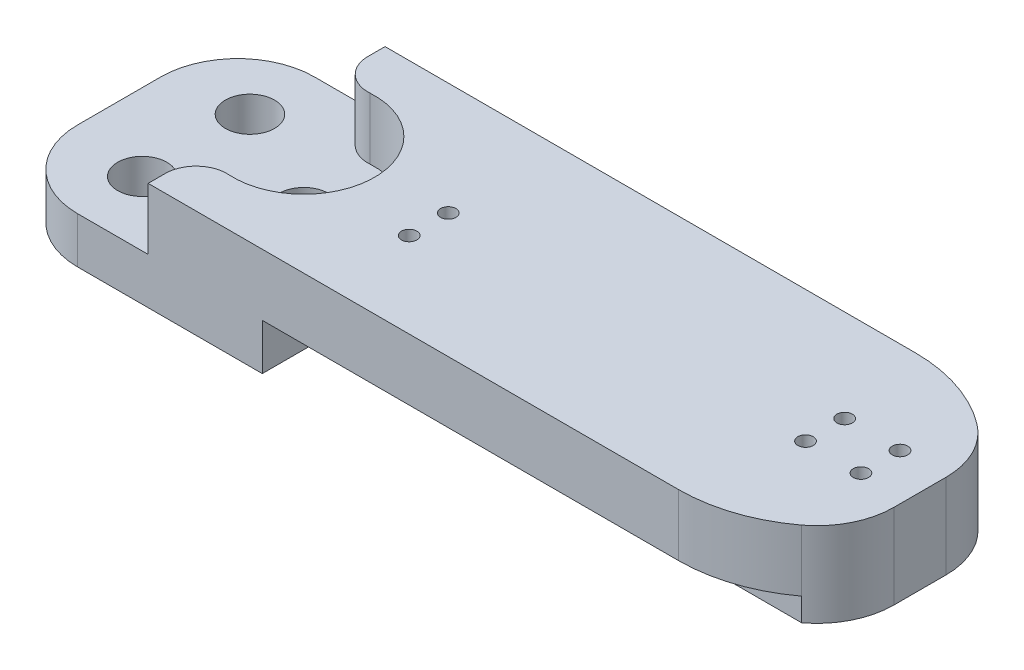
SolidWorks part; units mm, degrees
ref_plane "前视基准面" through (0, 0, 0) normal (0, 0, 1) x (1, 0, 0)
ref_plane "上视基准面" through (0, 0, 0) normal (0, 1, 0) x (1, 0, 0)
ref_plane "右视基准面" through (0, 0, 0) normal (1, 0, 0) x (0, 0, -1)
other "Configuration Table"
sketch "草图1" plane through (0, 0, 0) normal (0, 1, 0) x (1, 0, 0)
  line L0 (93.0116, 72.586) -> (93.0217, 72.586)
  line L1 (93.0116, 72.586) -> (93.0116, 72.6063)
  line L2 (93.0116, 72.586) -> (93.0217, 72.586)
  line L3 (93.0116, 72.586) -> (93.0116, 72.6063)
  line L4 (93.0116, 72.586) -> (93.0217, 72.586)
  line L5 (93.0116, 72.586) -> (93.0116, 72.6063)
  line L6 (103.9336, 94.432) -> (103.9437, 94.432)
  line L7 (103.9336, 94.432) -> (103.9336, 94.4523)
  line L8 (168.0366, 84.272) -> (168.0366, 84.2822)
  line L9 (168.0366, 84.272) -> (168.0163, 84.272)
  line L10 (158.1141, 95.514) -> (158.1039, 95.514)
  line L11 (158.1141, 95.514) -> (158.1141, 95.4938)
  line L12 (107.4956, 78.486) -> (107.4956, 78.4759)
  line L13 (107.4956, 78.486) -> (107.5158, 78.486)
  line L14 (161.3376, 94.432) -> (161.3477, 94.432)
  line L15 (161.3376, 94.432) -> (161.3376, 94.4523)
  line L16 (98.6366, 91.661) -> (98.6366, 91.6712)
  line L17 (98.6366, 91.661) -> (98.6163, 91.661)
  line L18 (100.7956, 90.686) -> (100.7956, 90.6962)
  line L19 (100.7956, 90.686) -> (100.7753, 90.686)
  line L20 (164.6396, 89.352) -> (164.6294, 89.352)
  line L21 (164.6396, 89.352) -> (164.6396, 89.3318)
  line L22 (94.7616, 80.161) -> (94.7514, 80.161)
  line L23 (94.7616, 80.161) -> (94.7616, 80.1408)
  line L24 (168.1956, 81.732) -> (168.1854, 81.732)
  line L25 (168.1956, 81.732) -> (168.1956, 81.7118)
  line L26 (178.2616, 97.586) -> (178.2514, 97.586)
  line L27 (178.2616, 97.586) -> (178.2616, 97.5658)
  line L28 (172.9366, 94.061) -> (172.9366, 94.0712)
  line L29 (172.9366, 94.061) -> (172.9163, 94.061)
  line L30 (113.8866, 87.236) -> (113.8764, 87.236)
  line L31 (113.8866, 87.236) -> (113.8866, 87.2158)
  line L32 (165.6556, 84.272) -> (165.6556, 84.2619)
  line L33 (165.6556, 84.272) -> (165.6758, 84.272)
  line L34 (115.6116, 92.886) -> (115.6116, 92.8759)
  line L35 (115.6116, 92.886) -> (115.6318, 92.886)
  line L36 (99.6366, 91.636) -> (99.6366, 91.6462)
  line L37 (99.6366, 91.636) -> (99.6163, 91.636)
  line L38 (106.2116, 94.486) -> (106.2217, 94.486)
  line L39 (106.2116, 94.486) -> (106.2116, 94.5063)
  line L40 (176.0696, 87.066) -> (176.0696, 87.0762)
  line L41 (176.0696, 87.066) -> (176.0493, 87.066)
  line L42 (175.5866, 82.236) -> (175.5967, 82.236)
  line L43 (175.5866, 82.236) -> (175.5866, 82.2563)
  line L44 (175.5616, 90.368) -> (175.5717, 90.368)
  line L45 (175.5616, 90.368) -> (175.5616, 90.3883)
  line L46 (95.0616, 85.036) -> (95.0514, 85.036)
  line L47 (95.0616, 85.036) -> (95.0616, 85.0158)
  line L48 (170.3616, 84.526) -> (170.3616, 84.5159)
  line L49 (170.3616, 84.526) -> (170.3818, 84.526)
  line L50 (156.2576, 97.48) -> (156.2576, 97.4699)
  line L51 (156.2576, 97.48) -> (156.2778, 97.48)
  line L52 (165.4016, 77.414) -> (165.4016, 77.4039)
  line L53 (165.4016, 77.414) -> (165.4218, 77.414)
  line L54 (166.1636, 90.368) -> (166.1737, 90.368)
  line L55 (166.1636, 90.368) -> (166.1636, 90.3883)
  line L56 (170.4816, 89.098) -> (170.4816, 89.1082)
  line L57 (170.4816, 89.098) -> (170.4613, 89.098)
  line L58 (114.7116, 89.836) -> (114.7116, 89.8462)
  line L59 (114.7116, 89.836) -> (114.6913, 89.836)
  line L60 (174.4366, 96.386) -> (174.4366, 96.3962)
  line L61 (174.4366, 96.386) -> (174.4163, 96.386)
  line L62 (186.9916, 88.59) -> (186.9916, 88.5799)
  line L63 (186.9916, 88.59) -> (187.0118, 88.59)
  line L64 (103.7141, 76.086) -> (103.7242, 76.086)
  line L65 (103.7141, 76.086) -> (103.7141, 76.1063)
  line L66 (184.9436, 88.0845) -> (184.9436, 88.0744)
  line L67 (184.9436, 88.0845) -> (184.9638, 88.0845)
  line L68 (122.8116, 84.011) -> (122.8217, 84.011)
  line L69 (122.8116, 84.011) -> (122.8116, 84.0313)
  line L70 (120.9516, 99.512) -> (120.9414, 99.512)
  line L71 (120.9516, 99.512) -> (120.9516, 99.4918)
  line L72 (173.1116, 80.97) -> (173.1116, 80.9802)
  line L73 (173.1116, 80.97) -> (173.0913, 80.97)
  line L74 (117.6116, 92.911) -> (117.6116, 92.9212)
  line L75 (117.6116, 92.911) -> (117.5913, 92.911)
  line L76 (112.3156, 92.908) -> (112.3257, 92.908)
  line L77 (112.3156, 92.908) -> (112.3156, 92.9283)
  line L78 (120.9516, 97.988) -> (120.9414, 97.988)
  line L79 (120.9516, 97.988) -> (120.9516, 97.9678)
  line L80 (163.1156, 87.32) -> (163.1156, 87.3099)
  line L81 (163.1156, 87.32) -> (163.1358, 87.32)
  line L82 (103.7141, 75.086) -> (103.7039, 75.086)
  line L83 (103.7141, 75.086) -> (103.7141, 75.0658)
  line L84 (116.6366, 92.886) -> (116.6366, 92.8962)
  line L85 (116.6366, 92.886) -> (116.6163, 92.886)
  line L86 (108.2516, 75.636) -> (108.2414, 75.636)
  line L87 (108.2516, 75.636) -> (108.2516, 75.6158)
  line L88 (185.9756, 88.082) -> (185.9756, 88.0922)
  line L89 (185.9756, 88.082) -> (185.9553, 88.082)
  line L90 (104.5616, 81.486) -> (104.5514, 81.486)
  line L91 (104.5616, 81.486) -> (104.5616, 81.4658)
  line L92 (101.8116, 90.686) -> (101.8116, 90.6962)
  line L93 (101.8116, 90.686) -> (101.7913, 90.686)
  line L94 (102.8616, 82.886) -> (102.8616, 82.8759)
  line L95 (102.8616, 82.886) -> (102.8818, 82.886)
  line L96 (106.2116, 95.486) -> (106.2217, 95.486)
  line L97 (106.2116, 95.486) -> (106.2116, 95.5063)
  line L98 (101.1396, 75.636) -> (101.1396, 75.6462)
  line L99 (101.1396, 75.636) -> (101.1193, 75.636)
  line L100 (97.0116, 90.486) -> (97.0014, 90.486)
  line L101 (97.0116, 90.486) -> (97.0116, 90.4658)
  line L102 (102.7866, 90.786) -> (102.7866, 90.7962)
  line L103 (102.7866, 90.786) -> (102.7663, 90.786)
  line L104 (167.7116, 87.911) -> (167.7116, 87.9009)
  line L105 (167.7116, 87.911) -> (167.7318, 87.911)
  line L106 (166.1636, 91.384) -> (166.1534, 91.384)
  line L107 (166.1636, 91.384) -> (166.1636, 91.3638)
  line L108 (97.0116, 89.486) -> (97.0014, 89.486)
  line L109 (97.0116, 89.486) -> (97.0116, 89.4658)
  line L110 (100.1236, 75.636) -> (100.1236, 75.6462)
  line L111 (100.1236, 75.636) -> (100.1033, 75.636)
  line L112 (172.0866, 80.62) -> (172.0866, 80.6302)
  line L113 (172.0866, 80.62) -> (172.0663, 80.62)
  line L114 (108.4991, 87.3235) -> (108.4991, 87.3337)
  line L115 (108.4991, 87.3235) -> (108.4788, 87.3235)
  line L116 (185.2136, 89.86) -> (185.2237, 89.86)
  line L117 (185.2136, 89.86) -> (185.2136, 89.8803)
  line L118 (173.2756, 88.844) -> (173.2756, 88.8339)
  line L119 (173.2756, 88.844) -> (173.2958, 88.844)
  line L120 (171.9366, 94.036) -> (171.9366, 94.0259)
  line L121 (171.9366, 94.036) -> (171.9568, 94.036)
  line L122 (170.2276, 93.924) -> (170.2276, 93.9139)
  line L123 (170.2276, 93.924) -> (170.2478, 93.924)
  line L124 (175.5866, 79.586) -> (175.5967, 79.586)
  line L125 (175.5866, 79.586) -> (175.5866, 79.6063)
  line L126 (180.5391, 83.002) -> (180.5492, 83.002)
  line L127 (180.5391, 83.002) -> (180.5391, 83.0223)
  line L128 (119.2116, 84.011) -> (119.2217, 84.011)
  line L129 (119.2116, 84.011) -> (119.2116, 84.0313)
  line L130 (107.7116, 74.186) -> (107.7217, 74.186)
  line L131 (107.7116, 74.186) -> (107.7116, 74.2063)
  line L132 (107.6116, 80.886) -> (107.6116, 80.8759)
  line L133 (107.6116, 80.886) -> (107.6318, 80.886)
  line L134 (103.7866, 91.561) -> (103.7866, 91.5712)
  line L135 (103.7866, 91.561) -> (103.7663, 91.561)
  line L136 (108.5866, 80.886) -> (108.5866, 80.8759)
  line L137 (108.5866, 80.886) -> (108.6068, 80.886)
  line L138 (165.5262, 99.6668) -> (182.5442, 99.6668)
  line L139 (182.5442, 99.6668) -> (182.5442, 96.8728)
  line L140 (96.8824, 77.3808) -> (96.6276, 77.6237)
  line L141 (96.6276, 77.6237) -> (96.3469, 77.836)
  line L142 (96.0438, 78.0149) -> (95.7224, 78.1582)
  line L143 (95.7224, 78.1582) -> (95.3867, 78.264)
  line L144 (164.7642, 100.4288) -> (165.5262, 99.6668)
  line L145 (164.5669, 88.1518) -> (164.4036, 88.0947)
  line L146 (164.4036, 88.0947) -> (164.2571, 88.0026)
  line L147 (164.2571, 88.0026) -> (164.1348, 87.8803)
  line L148 (164.1348, 87.8803) -> (164.0427, 87.7338)
  line L149 (164.1348, 86.917) -> (164.2571, 86.7947)
  line L150 (164.2571, 86.7947) -> (164.4036, 86.7026)
  line L151 (164.4036, 86.7026) -> (164.5669, 86.6455)
  line L152 (164.5669, 86.6455) -> (164.7388, 86.6261)
  line L153 (164.7388, 86.6261) -> (164.9107, 86.6455)
  line L154 (165.4919, 87.2267) -> (165.5113, 87.3986)
  line L155 (165.5113, 87.3986) -> (165.4919, 87.5705)
  line L156 (165.4919, 87.5705) -> (165.4348, 87.7338)
  line L157 (165.4348, 87.7338) -> (165.3427, 87.8803)
  line L158 (165.3427, 87.8803) -> (165.2204, 88.0026)
  line L159 (137.7132, 95.8568) -> (137.144, 95.8353)
  line L160 (151.1426, 85.7394) -> (151.3379, 85.9384)
  line L161 (151.8102, 87.2208) -> (151.7905, 87.499)
  line L162 (151.7905, 87.499) -> (151.7319, 87.7716)
  line L163 (151.7319, 87.7716) -> (151.6355, 88.0333)
  line L164 (151.6355, 88.0333) -> (151.5033, 88.2788)
  line L165 (151.5033, 88.2788) -> (151.3379, 88.5033)
  line L166 (139.9573, 95.5149) -> (139.4075, 95.6639)
  line L167 (139.4075, 95.6639) -> (138.8482, 95.7709)
  line L168 (138.8482, 95.7709) -> (138.2823, 95.8353)
  line L169 (138.2823, 95.8353) -> (137.7132, 95.8568)
  line L170 (118.0282, 100.4288) -> (164.7642, 100.4288)
  line L171 (182.5442, 96.8728) -> (182.6167, 96.5552)
  line L172 (118.0282, 98.6508) -> (118.0282, 100.4288)
  line L173 (182.6167, 96.5552) -> (182.7281, 96.249)
  line L174 (97.8352, 98.6508) -> (118.0282, 98.6508)
  line L175 (182.7281, 96.249) -> (182.8767, 95.9591)
  line L176 (97.8352, 94.5868) -> (97.8352, 98.6508)
  line L177 (182.8767, 95.9591) -> (183.0603, 95.6899)
  line L178 (97.8236, 94.2665) -> (97.8352, 94.5868)
  line L179 (183.0603, 95.6899) -> (183.2759, 95.4456)
  line L180 (97.7731, 93.95) -> (97.8236, 94.2665)
  line L181 (183.2759, 95.4456) -> (183.5202, 95.23)
  line L182 (97.6844, 93.642) -> (97.7731, 93.95)
  line L183 (183.5202, 95.23) -> (183.7894, 95.0464)
  line L184 (97.5587, 93.3471) -> (97.6844, 93.642)
  line L185 (183.7894, 95.0464) -> (184.0793, 94.8978)
  line L186 (97.398, 93.0697) -> (97.5587, 93.3471)
  line L187 (184.0793, 94.8978) -> (184.3855, 94.7864)
  line L188 (97.2046, 92.8141) -> (97.398, 93.0697)
  line L189 (184.3855, 94.7864) -> (184.7032, 94.7138)
  line L190 (96.9815, 92.5839) -> (97.2046, 92.8141)
  line L191 (184.7032, 94.7138) -> (188.8942, 94.7138)
  line L192 (96.732, 92.3827) -> (96.9815, 92.5839)
  line L193 (188.8942, 94.7138) -> (188.8942, 78.3308)
  line L194 (96.4599, 92.2134) -> (96.732, 92.3827)
  line L195 (188.8942, 78.3308) -> (177.4642, 78.3308)
  line L196 (96.169, 92.0786) -> (96.4599, 92.2134)
  line L197 (177.4642, 78.3308) -> (177.1354, 78.2515)
  line L198 (95.864, 91.9802) -> (96.169, 92.0786)
  line L199 (177.1354, 78.2515) -> (176.8186, 78.1328)
  line L200 (95.5492, 91.9198) -> (95.864, 91.9802)
  line L201 (176.8186, 78.1328) -> (176.5187, 77.9765)
  line L202 (93.0092, 91.9198) -> (95.5492, 91.9198)
  line L203 (176.5187, 77.9765) -> (176.2399, 77.7849)
  line L204 (93.0092, 88.1098) -> (93.0092, 91.9198)
  line L205 (176.2399, 77.7849) -> (175.9866, 77.5609)
  line L206 (95.5492, 88.1098) -> (93.0092, 88.1098)
  line L207 (175.9866, 77.5609) -> (175.7623, 77.3077)
  line L208 (95.7229, 88.0427) -> (95.5492, 88.1098)
  line L209 (175.7623, 77.3077) -> (175.5704, 77.0292)
  line L210 (95.878, 87.9395) -> (95.7229, 88.0427)
  line L211 (175.5704, 77.0292) -> (175.4138, 76.7294)
  line L212 (96.007, 87.8051) -> (95.878, 87.9395)
  line L213 (175.4138, 76.7294) -> (175.2949, 76.4128)
  line L214 (96.1038, 87.6459) -> (96.007, 87.8051)
  line L215 (175.2949, 76.4128) -> (175.2152, 76.084)
  line L216 (96.1638, 87.4695) -> (96.1038, 87.6459)
  line L217 (175.2152, 76.084) -> (175.1761, 75.7481)
  line L218 (96.1842, 87.2843) -> (96.1638, 87.4695)
  line L219 (175.1761, 75.7481) -> (175.1782, 75.4098)
  line L220 (96.1638, 87.0992) -> (96.1842, 87.2843)
  line L221 (175.1782, 75.4098) -> (175.1782, 75.0288)
  line L222 (96.1038, 86.9228) -> (96.1638, 87.0992)
  line L223 (175.1782, 75.0288) -> (161.4622, 75.0288)
  line L224 (96.007, 86.7636) -> (96.1038, 86.9228)
  line L225 (161.4622, 75.0288) -> (161.4622, 72.6158)
  line L226 (95.878, 86.6292) -> (96.007, 86.7636)
  line L227 (161.4622, 72.6158) -> (97.5812, 72.6158)
  line L228 (95.7229, 86.526) -> (95.878, 86.6292)
  line L229 (97.5812, 72.6158) -> (97.5812, 76.1718)
  line L230 (95.5492, 86.4588) -> (95.7229, 86.526)
  line L231 (97.5812, 76.1718) -> (97.4595, 76.5021)
  line L232 (93.0092, 86.4588) -> (95.5492, 86.4588)
  line L233 (97.4595, 76.5021) -> (97.301, 76.8164)
  line L234 (93.0092, 78.3308) -> (93.0092, 86.4588)
  line L235 (97.301, 76.8164) -> (97.1078, 77.1105)
  line L236 (95.0412, 78.3308) -> (93.0092, 78.3308)
  line L237 (97.1078, 77.1105) -> (96.8824, 77.3808)
  line L238 (95.3867, 78.264) -> (95.0412, 78.3308)
  line L239 (138.4395, 78.6481) -> (139.0038, 78.7263)
  line L240 (137.871, 78.6089) -> (138.4395, 78.6481)
  line L241 (137.3013, 78.6089) -> (137.871, 78.6089)
  line L242 (96.3469, 77.836) -> (96.0438, 78.0149)
  line L243 (164.7388, 88.1712) -> (164.5669, 88.1518)
  line L244 (164.9107, 88.1518) -> (164.7388, 88.1712)
  line L245 (165.0739, 88.0947) -> (164.9107, 88.1518)
  line L246 (165.2204, 88.0026) -> (165.0739, 88.0947)
  line L247 (134.0044, 79.4194) -> (134.5262, 79.1906)
  line L248 (133.4996, 79.6836) -> (134.0044, 79.4194)
  line L249 (133.0142, 79.9818) -> (133.4996, 79.6836)
  line L250 (123.9972, 85.6968) -> (133.0142, 79.9818)
  line L251 (123.8108, 85.8961) -> (123.9972, 85.6968)
  line L252 (165.4348, 87.0635) -> (165.4919, 87.2267)
  line L253 (165.3427, 86.917) -> (165.4348, 87.0635)
  line L254 (165.2204, 86.7947) -> (165.3427, 86.917)
  line L255 (165.0739, 86.7026) -> (165.2204, 86.7947)
  line L256 (164.9107, 86.6455) -> (165.0739, 86.7026)
  line L257 (123.3808, 87.4295) -> (123.3622, 87.1573)
  line L258 (123.4363, 87.6966) -> (123.3808, 87.4295)
  line L259 (123.5278, 87.9536) -> (123.4363, 87.6966)
  line L260 (123.6534, 88.1958) -> (123.5278, 87.9536)
  line L261 (123.8108, 88.4186) -> (123.6534, 88.1958)
  line L262 (164.0427, 87.0635) -> (164.1348, 86.917)
  line L263 (163.9856, 87.2267) -> (164.0427, 87.0635)
  line L264 (163.9662, 87.3986) -> (163.9856, 87.2267)
  line L265 (163.9856, 87.5705) -> (163.9662, 87.3986)
  line L266 (164.0427, 87.7338) -> (163.9856, 87.5705)
  line L267 (136.5782, 95.7709) -> (136.0188, 95.6639)
  line L268 (137.144, 95.8353) -> (136.5782, 95.7709)
  line L269 (186.4304, 92.0214) -> (186.4304, 93.139)
  line L270 (184.5508, 92.0214) -> (186.4304, 92.0214)
  line L271 (179.928, 93.139) -> (179.928, 92.0214)
  line L272 (181.8076, 93.139) -> (179.928, 93.139)
  line L273 (181.8076, 92.0214) -> (181.8076, 93.139)
  line L274 (140.4941, 95.3249) -> (139.9573, 95.5149)
  line L275 (141.0152, 95.0948) -> (140.4941, 95.3249)
  line L276 (150.9212, 88.8718) -> (141.0152, 95.0948)
  line L277 (151.1426, 88.7023) -> (150.9212, 88.8718)
  line L278 (151.3379, 88.5033) -> (151.1426, 88.7023)
  line L279 (176.7784, 94.9678) -> (176.7784, 93.0882)
  line L280 (177.896, 94.9678) -> (176.7784, 94.9678)
  line L281 (177.896, 93.0882) -> (177.896, 94.9678)
  line L282 (176.7784, 93.0882) -> (177.896, 93.0882)
  line L283 (171.038, 98.3206) -> (171.038, 97.203)
  line L284 (151.7905, 86.9427) -> (151.8102, 87.2208)
  line L285 (151.7319, 86.6701) -> (151.7905, 86.9427)
  line L286 (151.6355, 86.4084) -> (151.7319, 86.6701)
  line L287 (151.5033, 86.1629) -> (151.6355, 86.4084)
  line L288 (151.3379, 85.9384) -> (151.5033, 86.1629)
  line L289 (163.4688, 97.3554) -> (163.4688, 98.473)
  line L290 (150.9212, 85.5698) -> (151.1426, 85.7394)
  line L291 (142.1582, 79.9818) -> (150.9212, 85.5698)
  line L292 (141.6727, 79.6836) -> (142.1582, 79.9818)
  line L293 (141.1679, 79.4194) -> (141.6727, 79.6836)
  line L294 (140.6461, 79.1906) -> (141.1679, 79.4194)
  line L295 (140.1098, 78.9982) -> (140.6461, 79.1906)
  line L296 (139.5615, 78.8432) -> (140.1098, 78.9982)
  line L297 (139.0038, 78.7263) -> (139.5615, 78.8432)
  line L298 (136.7328, 78.6481) -> (137.3013, 78.6089)
  line L299 (136.1685, 78.7263) -> (136.7328, 78.6481)
  line L300 (135.6108, 78.8432) -> (136.1685, 78.7263)
  line L301 (135.0625, 78.9982) -> (135.6108, 78.8432)
  line L302 (134.5262, 79.1906) -> (135.0625, 78.9982)
  line L303 (134.4112, 95.0948) -> (123.9972, 88.6178)
  line L304 (134.9322, 95.3249) -> (134.4112, 95.0948)
  line L305 (179.928, 92.0214) -> (181.8076, 92.0214)
  line L306 (182.2648, 93.9518) -> (182.2648, 92.8342)
  line L307 (184.1444, 93.9518) -> (182.2648, 93.9518)
  line L308 (123.6534, 86.1189) -> (123.8108, 85.8961)
  line L309 (123.5278, 86.3611) -> (123.6534, 86.1189)
  line L310 (123.4363, 86.6181) -> (123.5278, 86.3611)
  line L311 (123.3808, 86.8852) -> (123.4363, 86.6181)
  line L312 (123.3622, 87.1573) -> (123.3808, 86.8852)
  line L313 (135.469, 95.5149) -> (134.9322, 95.3249)
  line L314 (136.0188, 95.6639) -> (135.469, 95.5149)
  line L315 (172.9176, 98.3206) -> (171.038, 98.3206)
  line L316 (172.9176, 97.203) -> (172.9176, 98.3206)
  line L317 (171.038, 97.203) -> (172.9176, 97.203)
  line L318 (123.9972, 88.6178) -> (123.8108, 88.4186)
  line L319 (161.5892, 98.473) -> (161.5892, 97.3554)
  line L320 (163.4688, 98.473) -> (161.5892, 98.473)
  line L321 (157.6268, 97.3554) -> (159.5064, 97.3554)
  line L322 (161.5892, 97.3554) -> (163.4688, 97.3554)
  line L323 (159.5064, 98.473) -> (157.6268, 98.473)
  line L324 (159.5064, 97.3554) -> (159.5064, 98.473)
  line L325 (184.1444, 92.8342) -> (184.1444, 93.9518)
  line L326 (186.4304, 93.139) -> (184.5508, 93.139)
  line L327 (184.5508, 93.139) -> (184.5508, 92.0214)
  line L328 (182.2648, 92.8342) -> (184.1444, 92.8342)
  line L329 (157.6268, 98.473) -> (157.6268, 97.3554)
  line L330 (119.5316, 81.791) -> (119.5316, 81.151)
  line L331 (118.8916, 81.151) -> (119.5316, 81.151)
  line L332 (118.8916, 81.791) -> (118.8916, 81.151)
  line L333 (118.8916, 81.791) -> (119.5316, 81.791)
  line L334 (119.5316, 84.331) -> (119.5316, 83.691)
  line L335 (118.8916, 84.331) -> (118.8916, 83.691)
  line L336 (118.8916, 84.331) -> (119.5316, 84.331)
  line L337 (118.8916, 83.691) -> (119.5316, 83.691)
  line L338 (122.4916, 81.791) -> (123.1316, 81.791)
  line L339 (122.4916, 81.151) -> (123.1316, 81.151)
  line L340 (122.4916, 81.791) -> (122.4916, 81.151)
  line L341 (123.1316, 81.791) -> (123.1316, 81.151)
  line L342 (123.1316, 84.331) -> (123.1316, 83.691)
  line L343 (122.4916, 83.691) -> (123.1316, 83.691)
  line L344 (122.4916, 84.331) -> (123.1316, 84.331)
  line L345 (122.4916, 84.331) -> (122.4916, 83.691)
  line L346 (94.4416, 79.841) -> (94.4416, 80.481)
  line L347 (95.0816, 80.481) -> (94.4416, 80.481)
  line L348 (95.0816, 79.841) -> (94.4416, 79.841)
  line L349 (95.0816, 79.841) -> (95.0816, 80.481)
  line L350 (94.4416, 82.381) -> (94.4416, 83.021)
  line L351 (95.0816, 83.021) -> (94.4416, 83.021)
  line L352 (95.0816, 82.381) -> (94.4416, 82.381)
  line L353 (95.0816, 82.381) -> (95.0816, 83.021)
  circle A0 centre (122.8116, 81.471) radius 0.5
  circle A1 centre (107.2241, 88.5985) radius 0.175
  circle A2 centre (109.7741, 86.0485) radius 0.175
  circle A3 centre (108.4991, 86.0485) radius 0.175
  circle A4 centre (107.2241, 86.0485) radius 0.175
  circle A5 centre (119.2116, 81.471) radius 0.5
  circle A6 centre (94.7616, 80.161) radius 0.5
  circle A7 centre (94.7616, 82.701) radius 0.5
  circle A8 centre (122.8116, 84.011) radius 0.5
  circle A9 centre (119.2116, 84.011) radius 0.5
  circle A10 centre (109.7741, 87.3235) radius 0.175
  circle A11 centre (108.4991, 87.3235) radius 0.175
  circle A12 centre (107.2241, 87.3235) radius 0.175
  circle A13 centre (109.7741, 88.5985) radius 0.175
  circle A14 centre (108.4991, 88.5985) radius 0.175
  point P204 (93.0116, 72.586)
  point P205 (93.0116, 72.586)
  point P206 (93.0116, 72.586)
  point P207 (103.9336, 94.432)
  point P208 (168.0366, 84.272)
  point P209 (158.1141, 95.514)
  point P210 (107.4956, 78.486)
  point P211 (161.3376, 94.432)
  point P212 (98.6366, 91.661)
  point P213 (100.7956, 90.686)
  point P214 (164.6396, 89.352)
  point P215 (94.7616, 80.161)
  point P216 (168.1956, 81.732)
  point P217 (178.2616, 97.586)
  point P218 (172.9366, 94.061)
  point P219 (113.8866, 87.236)
  point P220 (165.6556, 84.272)
  point P221 (115.6116, 92.886)
  point P222 (99.6366, 91.636)
  point P223 (106.2116, 94.486)
  point P224 (176.0696, 87.066)
  point P225 (175.5866, 82.236)
  point P226 (175.5616, 90.368)
  point P227 (95.0616, 85.036)
  point P228 (170.3616, 84.526)
  point P229 (156.2576, 97.48)
  point P230 (165.4016, 77.414)
  point P231 (166.1636, 90.368)
  point P232 (170.4816, 89.098)
  point P233 (114.7116, 89.836)
  point P234 (174.4366, 96.386)
  point P235 (186.9916, 88.59)
  point P236 (103.7141, 76.086)
  point P237 (184.9436, 88.0845)
  point P238 (122.8116, 84.011)
  point P239 (120.9516, 99.512)
  point P240 (173.1116, 80.97)
  point P241 (117.6116, 92.911)
  point P242 (112.3156, 92.908)
  point P243 (120.9516, 97.988)
  point P244 (163.1156, 87.32)
  point P245 (103.7141, 75.086)
  point P246 (116.6366, 92.886)
  point P247 (108.2516, 75.636)
  point P248 (185.9756, 88.082)
  point P249 (104.5616, 81.486)
  point P250 (101.8116, 90.686)
  point P251 (102.8616, 82.886)
  point P252 (106.2116, 95.486)
  point P253 (101.1396, 75.636)
  point P254 (97.0116, 90.486)
  point P255 (102.7866, 90.786)
  point P256 (167.7116, 87.911)
  point P257 (166.1636, 91.384)
  point P258 (97.0116, 89.486)
  point P259 (100.1236, 75.636)
  point P260 (172.0866, 80.62)
  point P261 (108.4991, 87.3235)
  point P262 (185.2136, 89.86)
  point P263 (173.2756, 88.844)
  point P264 (171.9366, 94.036)
  point P265 (170.2276, 93.924)
  point P266 (175.5866, 79.586)
  point P267 (180.5391, 83.002)
  point P268 (119.2116, 84.011)
  point P269 (107.7116, 74.186)
  point P270 (107.6116, 80.886)
  point P271 (103.7866, 91.561)
  point P272 (108.5866, 80.886)
sketch "草图2" plane through (0, 0, 0) normal (0, 1, 0) x (1, 0, 0)
  line L1 (125.8116, 76.6158) -> (90.7616, 76.6158)
  line L2 (125.8116, 76.6158) -> (125.8116, 88.011)
  line L3 (125.8116, 88.011) -> (90.7616, 88.011)
  line L4 (90.7616, 76.6158) -> (90.7616, 88.011)
  line L5 (125.8116, 76.6158) -> (90.7616, 88.011) construction
  line L6 (125.8116, 88.011) -> (90.7616, 76.6158) construction
  line L7 (161.4622, 72.6158) -> (97.5812, 72.6158) construction
  circle A0 centre (94.7616, 82.701) radius 0.6
  circle A1 centre (94.7616, 80.161) radius 0.6
  circle A2 centre (119.2116, 84.011) radius 0.6
  circle A3 centre (122.8116, 84.011) radius 0.6
  circle A4 centre (122.8116, 81.471) radius 0.6
  circle A5 centre (119.2116, 81.471) radius 0.6
  point P0 (94.7616, 82.701)
  point P1 (94.7616, 80.161)
  point P3 (119.2116, 84.011)
  point P5 (119.2116, 81.471)
  point P7 (122.8116, 84.011)
  point P9 (122.8116, 81.471)
  point P28 (108.2866, 82.3134)
  dimension "D1" = 1.2
  dimension "D2" = 3
  dimension "D3" = 4
  dimension "D4" = 4
  dimension "D5" = 4
extrude "凸台-拉伸1" add sketch "草图2" along normal blind 1.5
sketch "草图3" plane through (0, 1.5, 0) normal (0, 1, 0) x (1, 0, 0)
  line L12 (127.8116, 74.6158) -> (127.8116, 90.011)
  line L13 (127.8116, 90.011) -> (88.7616, 90.011)
  line L14 (88.7616, 90.011) -> (88.7616, 74.6158)
  line L15 (88.7616, 74.6158) -> (127.8116, 74.6158)
  line L16 (127.8116, 74.6158) -> (127.8116, 90.011)
  line L17 (127.8116, 90.011) -> (88.7616, 90.011)
  line L18 (88.7616, 90.011) -> (88.7616, 74.6158)
  line L19 (88.7616, 74.6158) -> (127.8116, 74.6158)
  circle A2 centre (94.7616, 82.701) radius 0.5
  circle A5 centre (94.7616, 80.161) radius 0.5
  circle A8 centre (119.2116, 84.011) radius 0.5
  circle A11 centre (122.8116, 84.011) radius 0.5
  circle A14 centre (122.8116, 81.471) radius 0.5
  circle A16 centre (119.2116, 81.471) radius 0.5
  dimension "D1" = 1
  dimension "D7" = 2
extrude "凸台-拉伸2" add sketch "草图3" along normal blind 4
sketch "草图4" plane through (0, 0, -90.011) normal (0, 0, -1) x (-1, 0, 0)
  line L0 (-127.8116, 1.5) -> (-88.7616, 1.5) construction
  line L1 (-88.7616, 5.5) -> (-73.7616, 5.5)
  line L2 (-88.7616, 5.5) -> (-88.7616, 1.5)
  line L3 (-88.7616, 1.5) -> (-73.7616, 1.5)
  line L4 (-73.7616, 5.5) -> (-73.7616, 1.5)
  line L5 (-88.7616, 5.5) -> (-73.7616, 1.5) construction
  line L6 (-88.7616, 1.5) -> (-73.7616, 5.5) construction
  point P4 (-81.2616, 3.5)
  dimension "D1" = 15
extrude "凸台-拉伸3" add sketch "草图4" against normal up to surface (15.3952 mm away) up to face at (108.2866, 3.5, -74.6158)
sketch "草图5" plane through (0, 1.5, 0) normal (0, -1, 0) x (1, 0, 0)
  line L0 (127.8116, -90.011) -> (73.7616, -90.011) construction
  line L1 (73.7616, -74.6158) -> (90.7616, -74.6158)
  line L2 (73.7616, -74.6158) -> (73.7616, -90.011)
  line L3 (73.7616, -90.011) -> (90.7616, -90.011)
  line L4 (90.7616, -74.6158) -> (90.7616, -90.011)
  line L5 (73.7616, -74.6158) -> (90.7616, -90.011) construction
  line L6 (73.7616, -90.011) -> (90.7616, -74.6158) construction
  line L7 (90.7616, -88.011) -> (90.7616, -76.6158) construction
  point P4 (82.2616, -82.3134)
extrude "凸台-拉伸4" add sketch "草图5" along normal blind 3
sketch "草图6" plane through (0, -1.5, 0) normal (0, -1, 0) x (1, 0, 0)
  line L0 (73.7616, -82.3134) -> (90.7616, -82.3134) construction
  line L1 (73.7616, -74.6158) -> (73.7616, -90.011) construction
  line L2 (90.7616, -88.011) -> (90.7616, -76.6158) construction
  line L3 (78.7616, -74.6158) -> (78.7616, -90.011) construction
  line L4 (90.7616, -74.6158) -> (73.7616, -74.6158) construction
  line L5 (73.7616, -90.011) -> (90.7616, -90.011) construction
  circle A0 centre (78.7616, -78.8134) radius 1.6
  circle A1 centre (85.7616, -82.3134) radius 1.6
  circle A2 centre (78.7616, -85.8134) radius 1.6
  dimension "D1" = 3.2
  dimension "D2" = 7
  dimension "D3" = 7
  dimension "D4" = 5
extrude "切除-拉伸1" cut sketch "草图6" against normal through all
sketch "草图7" plane through (0, 5.5, 0) normal (0, 1, 0) x (1, 0, 0)
  circle A0 centre (78.7616, 85.8134) radius 1.6 construction
  arc A1 (83.343, 86.2263) -> (75.7766, 82.3134) centre (78.7616, 85.8134) ccw
  circle A8 centre (85.7616, 82.3134) radius 4.6
  arc A9 (83.343, 78.4006) -> (83.343, 86.2263) centre (85.7616, 82.3134) ccw
  circle A11 centre (78.7616, 78.8134) radius 4.6
  arc A12 (75.7766, 82.3134) -> (83.343, 78.4006) centre (78.7616, 78.8134) ccw
  dimension "D1" = 3
  dimension "D2" = 3
  dimension "D3" = 3
extrude "切除-拉伸2" cut sketch "草图7" against normal offset from surface (4 mm away) 3 up to face at (78.7616, -1.5, -80.4134)
sketch "草图8" plane through (0, 5.5, 0) normal (0, 1, 0) x (1, 0, 0)
  line L0 (89.6957, 79.9296) -> (83.343, 78.4006)
  line L1 (83.343, 78.4006) -> (80.6431, 74.6158)
  line L2 (80.6431, 74.6158) -> (92.689, 74.6158)
  line L9 (127.8116, 90.011) -> (80.6431, 90.011) construction
  line L10 (80.6431, 74.6158) -> (127.8116, 74.6158) construction
  line L11 (92.689, 90.011) -> (80.6431, 90.011)
  line L15 (80.6431, 90.011) -> (83.343, 86.2263)
  line L16 (83.343, 86.2263) -> (89.6957, 84.6973)
  line L18 (76.88, 90.011) -> (73.7616, 90.011)
  line L19 (73.7616, 90.011) -> (73.7616, 74.6158)
  line L20 (73.7616, 74.6158) -> (76.88, 74.6158)
  line L21 (76.88, 90.011) -> (73.7616, 90.011)
  line L22 (73.7616, 90.011) -> (73.7616, 74.6158)
  line L23 (73.7616, 74.6158) -> (76.88, 74.6158)
  arc A8 (92.689, 90.011) -> (89.6957, 84.6973) centre (92.689, 86.511) ccw
  arc A9 (89.6957, 79.9296) -> (92.689, 74.6158) centre (92.689, 78.1158) ccw
  arc A10 (83.343, 78.4006) -> (83.343, 86.2263) centre (85.7616, 82.3134) ccw construction
  arc A11 (83.343, 78.4006) -> (83.343, 86.2263) centre (85.7616, 82.3134) ccw construction
  arc A16 (76.88, 90.011) -> (75.7766, 82.3134) centre (78.7616, 85.8134) ccw
  arc A17 (75.7766, 82.3134) -> (76.88, 74.6158) centre (78.7616, 78.8134) ccw
  arc A18 (76.88, 90.011) -> (75.7766, 82.3134) centre (78.7616, 85.8134) ccw
  arc A19 (75.7766, 82.3134) -> (76.88, 74.6158) centre (78.7616, 78.8134) ccw
  dimension "D1" = 7
  dimension "D2" = 0
extrude "切除-拉伸4" cut sketch "草图8" against normal up to surface (4 mm away) contours A18 A19 L23 L22 L21 up to face at (85.7616, 1.5, -83.9134)
fillet "圆角2" radius 5 2 edges at (73.7616, 0, -90.011) (73.7616, 0, -74.6158)
sketch "草图9" plane through (0, 5.5, 0) normal (0, 1, 0) x (1, 0, 0)
  line L0 (83.343, 86.2263) -> (83.343, 90.011)
  line L1 (127.8116, 90.011) -> (80.6431, 90.011) construction
  line L2 (83.343, 90.011) -> (80.6431, 90.011)
  line L3 (80.6431, 90.011) -> (83.343, 86.2263)
  line L4 (83.343, 78.4006) -> (83.343, 74.6158)
  line L5 (80.6431, 74.6158) -> (127.8116, 74.6158) construction
  line L6 (83.343, 74.6158) -> (80.6431, 74.6158)
  line L7 (80.6431, 74.6158) -> (83.343, 78.4006)
extrude "切除-拉伸5" cut sketch "草图9" against normal up to surface (4 mm away) up to face at (79.8741, 1.5, -82.3134)
fillet "圆角3" radius 2 2 edges at (83.343, 3.5, -78.4006) (83.343, 3.5, -86.2263)
sketch "草图10" plane through (0, -1.5, 0) normal (0, -1, 0) x (1, 0, 0)
  line L0 (85.7616, -82.3134) -> (85.7616, -73.1344) construction
  line L1 (81.7616, -82.3134) -> (88.5604, -82.3134) construction
  circle A0 centre (81.7616, -82.3134) radius 0.6
  circle A1 centre (85.7616, -77.3134) radius 0.6
  circle A2 centre (85.7616, -87.3134) radius 0.6
  dimension "D3" = 1.2
  dimension "D1" = 10
  dimension "D2" = 4
extrude "切除-拉伸6" cut sketch "草图10" against normal blind 2
sketch "草图11" plane through (0, 0, 0) normal (0, -1, 0) x (1, 0, 0)
  line L0 (127.8116, -74.6158) -> (127.8116, -90.011) construction
  line L1 (90.7616, -74.6158) -> (127.8116, -74.6158) construction
  line L2 (127.8116, -90.011) -> (90.7616, -90.011) construction
  line L3 (117.8116, -74.6158) -> (127.8116, -74.6158)
  line L4 (127.8116, -74.6158) -> (127.8116, -84.6158)
  line L5 (127.8116, -90.011) -> (117.8116, -90.011)
  line L6 (127.8116, -80.011) -> (127.8116, -90.011)
  arc A0 (126.6883, -80.011) -> (117.8116, -74.6158) centre (117.8116, -84.6158) ccw
  arc A1 (117.8116, -90.011) -> (126.6883, -84.6158) centre (117.8116, -80.011) ccw
  arc A2 (126.6883, -84.6158) -> (126.6883, -80.011) centre (122.2499, -82.3134) ccw
  line M3 (125.8116, -88.011) -> (125.8116, -76.6158)
  line M4 (125.8116, -76.6158) -> (90.7616, -76.6158)
  line M6 (90.7616, -88.011) -> (125.8116, -88.011)
  dimension "D1" = 20
  dimension "D2" = 10
extrude "切除-拉伸7" cut sketch "草图11" against normal through all contours A2 A1 L5 L6 L4 L3 A0 M3 M6 M4 | A0 M3 M4 | A1 M6 M3 region at (122.8116, 0, -74.7994) region at (125.1768, 0, -77.2506) region at (125.1768, 0, -87.3763)
sketch "草图12" plane through (0, 1.5, 0) normal (0, -1, 0) x (1, 0, 0)
  line L2 (125.8116, -78.6158) -> (125.8116, -86.011)
  line L3 (125.8116, -78.6158) -> (125.8116, -86.011)
  arc A8 (125.8116, -86.011) -> (126.6883, -84.6158) centre (117.8116, -80.011) ccw
  arc A9 (126.6883, -84.6158) -> (126.6883, -80.011) centre (122.2499, -82.3134) ccw
  arc A10 (126.6883, -80.011) -> (125.8116, -78.6158) centre (117.8116, -84.6158) ccw
  arc A11 (125.8116, -86.011) -> (126.6883, -84.6158) centre (117.8116, -80.011) ccw
  arc A12 (126.6883, -84.6158) -> (126.6883, -80.011) centre (122.2499, -82.3134) ccw
  arc A13 (126.6883, -80.011) -> (125.8116, -78.6158) centre (117.8116, -84.6158) ccw
  dimension "D1" = 0
extrude "切除-拉伸8" cut sketch "草图12" against normal through all
fillet "圆角5" radius 5 2 edges at (125.8116, 2.75, -86.011) (125.8116, 2.75, -78.6158)
